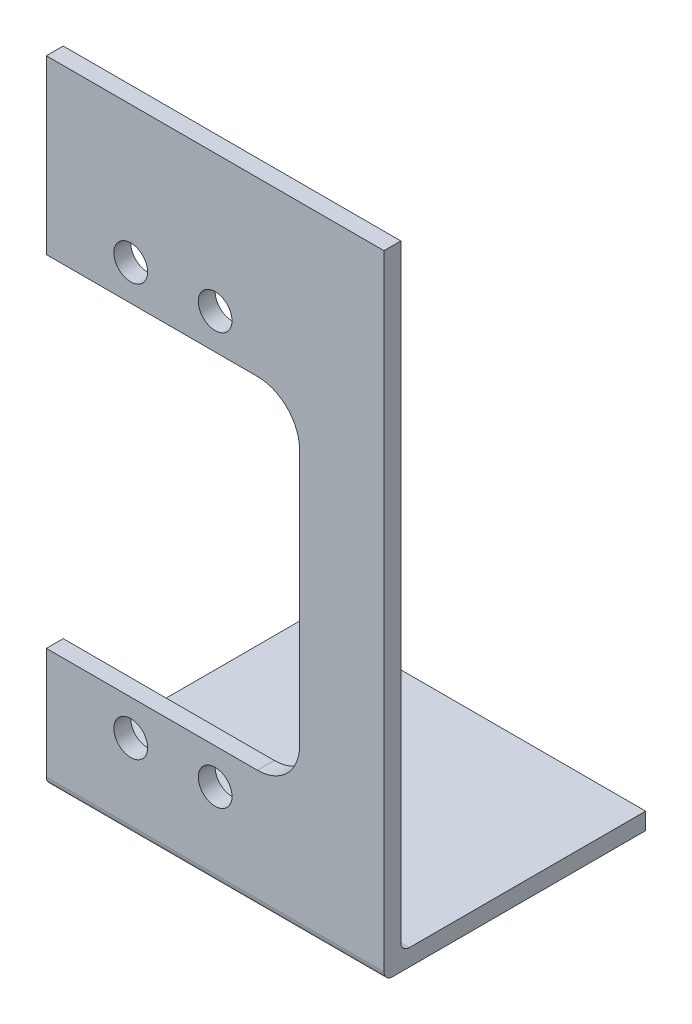
SolidWorks part; units mm, degrees
ref_plane "Front Plane" through (0, 0, 0) normal (0, 0, 1) x (1, 0, 0)
ref_plane "Top Plane" through (0, 0, 0) normal (0, 1, 0) x (1, 0, 0)
ref_plane "Right Plane" through (0, 0, 0) normal (1, 0, 0) x (0, 0, -1)
sketch "Sketch1" plane through (0, 0, 0) normal (0, 1, 0) x (1, 0, 0)
  line L1 (0, 0) -> (40, 0)
  line L2 (0, 0) -> (0, 30)
  line L3 (0, 30) -> (40, 30)
  line L4 (40, 0) -> (40, 30)
  dimension "D1" = 30
  dimension "D2" = 40
extrude "Boss-Extrude1" add sketch "Sketch1" along normal blind 2
sketch "Sketch2" plane through (0, 2, 0) normal (0, 1, 0) x (1, 0, 0)
  line L0 (40, 0) -> (40, 30) construction
  line L1 (0, 0) -> (40, 0)
  line L2 (0, 0) -> (0, 1)
  line L3 (0, 1) -> (40, 1)
  line L4 (40, 0) -> (40, 1)
  line L6 (0, 0) -> (40, 0)
  line L7 (0, 0) -> (0, -1)
  line L8 (0, -1) -> (40, -1)
  line L9 (40, 0) -> (40, -1)
  line M1 (0, 30) -> (0, 0)
  line M2 (0, 0) -> (40, 0)
  line M3 (40, 0) -> (40, 30)
  dimension "D1" = 1
  dimension "D2" = 1
extrude "Boss-Extrude2" add sketch "Sketch2" along normal blind 73 and the other way blind 2 contours L3 M1 M2 M3 | L9 L7 L8 M2 region at (20, 2, -0.5) region at (20, 2, 0.5)
fillet "Fillet1" radius 1 2 edges at (20, 0, 1) (20, 2, -1)
sketch "Sketch5" plane through (0, 2, 0) normal (0, 1, 0) x (1, 0, 0)
  line L0 (40, 2) -> (40, 30) construction
  line L1 (40, 30) -> (0, 30) construction
  circle A0 centre (20, 15) radius 1.5
  dimension "D1" = 20
  dimension "D2" = 15
hole_wizard "M3 Tapped Hole1" positions "Sketch6" profile "Sketch7" tap size "M3" standard "ISO" end condition through all
sketch "Sketch6" plane through (0, 2, 0) normal (0, 1, 0) x (1, 0, 0)
  point P0 (20, 15)
sketch "Sketch7" plane through (20, 2, -15) normal (1, 0, 0) x (0, 0, 1)
  line L0 (0, 0) -> (0, 2)
  line L1 (0, 2) -> (1.25, 2)
  line L2 (1.25, 2) -> (1.25, 0.275)
  line L3 (1.25, 0.275) -> (1.525, 0)
  line L5 (1.525, 0) -> (0, 0)
  line L6 (-1.25, 0.275) -> (-1.525, 0) construction
  line L11 (0, -6.35) -> (0, 107.95) construction
  dimension "Thru Tap Drill Dia." = 2.5
  dimension "Thru Tap Drill Depth" = 2
  dimension "Near C'Sink Dia." = 3.05
  dimension "Near C'Sink Angle" = 90
cosmetic thread "Hole Thread1" parameters "D2"=3
sketch "Sketch11" plane through (0, 0, 1) normal (0, 0, 1) x (1, 0, 0)
  line L0 (0, 1) -> (0, 75) construction
  line L1 (10, 58.8) -> (20, 58.8)
  line L2 (10, 58.8) -> (10, 10)
  line L3 (10, 10) -> (20, 10)
  line L4 (20, 58.8) -> (20, 10)
  line L5 (0, 75) -> (40, 75) construction
  line L7 (40, 0) -> (0, 0) construction
  line L8 (0, 54.6) -> (30, 54.6)
  line L9 (0, 54.6) -> (0, 14.2)
  line L10 (0, 14.2) -> (30, 14.2)
  line L11 (30, 54.6) -> (30, 14.2)
  circle A0 centre (10, 58.8) radius 2
  circle A1 centre (20, 58.8) radius 2
  circle A4 centre (10, 10) radius 2
  circle A5 centre (20, 10) radius 2
  line M7 (0, 75) -> (0, 1)
  dimension "D1" = 48.8
  dimension "D7" = 4.2
  dimension "D8" = 4.2
  dimension "D2" = 10
  dimension "D3" = 10
  dimension "D4" = 16.2
  dimension "D5" = 10
  dimension "D6" = 40.4
  dimension "D9" = 30
extrude "Cut-Extrude5" cut sketch "Sketch11" against normal blind 2 contours L10 L2 L8 M7 | L2 L10 L4 L8 | L1 A0 L2 | L2 A0 L1 | L1 A1 L4 | L4 A1 L1 | L2 A4 L3 | L3 A4 L2 | L3 A5 L4 | L4 A5 L3 | L11 L8 L4 L10 region at (9.7171, 59.0829, 1) region at (10.8488, 57.9512, 1) region at (20.2829, 59.0829, 1) region at (19.1512, 57.9512, 1) region at (15, 34.4, 1) region at (5, 34.4, 1) region at (25, 34.4, 1) region at (10.8488, 10.8488, 1) region at (9.7171, 9.7171, 1) region at (20.2829, 9.7171, 1) region at (19.1512, 10.8488, 1)
fillet "Fillet3" radius 5 2 edges at (30, 14.2, 0) (30, 54.6, 0)
